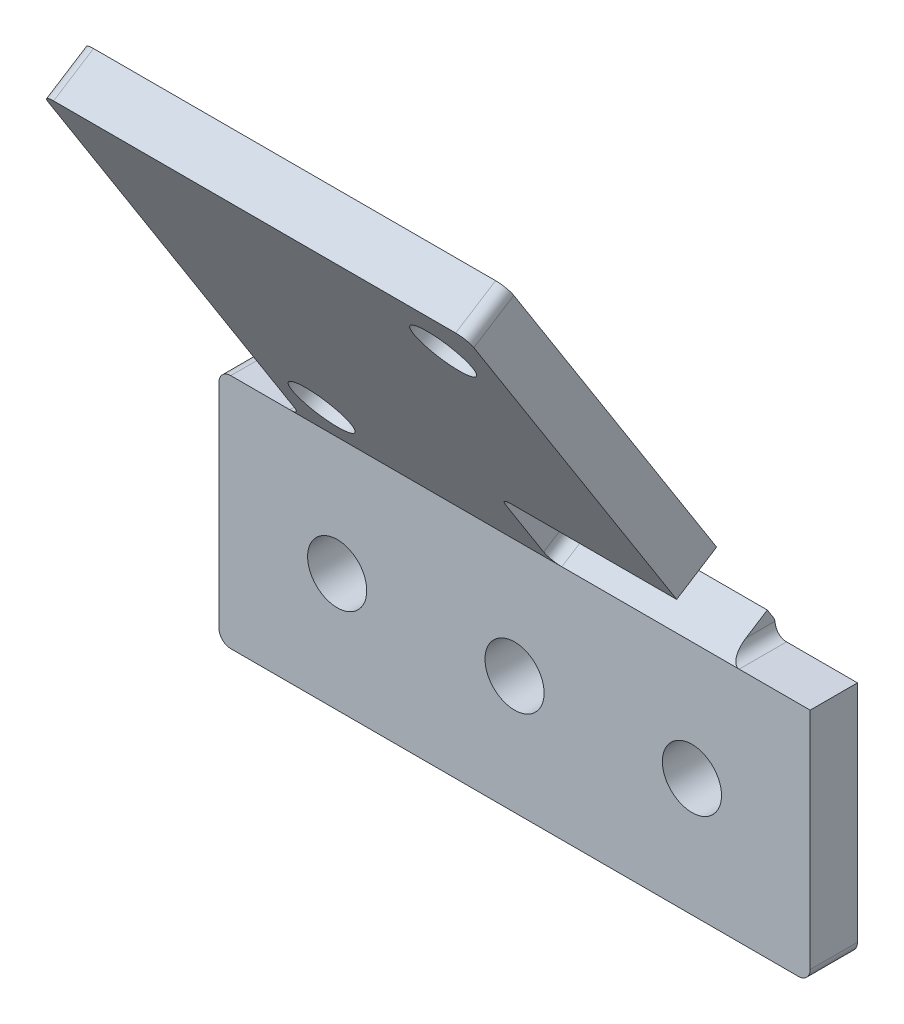
SolidWorks part; units mm, degrees
ref_plane "前视基准面" through (0, 0, 0) normal (0, 0, 1) x (1, 0, 0)
ref_plane "上视基准面" through (0, 0, 0) normal (0, 1, 0) x (1, 0, 0)
ref_plane "右视基准面" through (0, 0, 0) normal (1, 0, 0) x (0, 0, -1)
sketch "草图1" plane through (0, 0, 0) normal (0, 0, 1) x (1, 0, 0)
  line L1 (25, -10) -> (-25, -10)
  line L2 (25, -10) -> (25, 10)
  line L3 (25, 10) -> (-25, 10)
  line L4 (-25, -10) -> (-25, 10)
  line L5 (25, -10) -> (-25, 10) construction
  line L6 (25, 10) -> (-25, -10) construction
  point P0 (0, 0)
  dimension "D1" = 20
  dimension "D2" = 50
extrude "凸台-拉伸1" add sketch "草图1" along normal blind 4
sketch "草图4" plane through (0, 0, 0) normal (1, 0, 0) x (0, 0, -1)
  line L0 (-4, 10) -> (-25.9804, 44.6101)
  line L1 (-25.9804, 44.6101) -> (-22.6038, 46.7546)
  line L2 (-22.6038, 46.7546) -> (0.0489, 11.0858)
  line L3 (0.0489, 11.0858) -> (0, 10)
  line L4 (-4, 10) -> (0, 10)
  dimension "D1" = 145
  dimension "D2" = 41
  dimension "D3" = 4
extrude "凸台-拉伸2" add sketch "草图4" along normal mid plane 36
sketch "草图5" plane through (0, 1.0639, -1.6752) normal (0, -0.5361, 0.8441) x (1, 0, 0)
  line L0 (18, 51.5859) -> (-18, 10.5859) construction
  circle A2 centre (12.7216, 45.5744) radius 1.5
  circle A3 centre (-13.6705, 15.5168) radius 1.5
  dimension "D1" = 8
  dimension "D2" = 3
  dimension "D3" = 3
  dimension "D4" = 40
extrude "切除-拉伸1" cut sketch "草图5" against normal through all contours A2 | A2 | A3 | A3 region at (12.7216, 39.5355, 22.7576) region at (-13.6705, 14.1624, 6.6435)
sketch "草图6" plane through (0, 1.0639, -1.6752) normal (0, -0.5361, 0.8441) x (1, 0, 0)
  line L1 (18, 10.5859) -> (3, 10.5859)
  line L2 (18, 10.5859) -> (18, 18.5859)
  line L3 (18, 18.5859) -> (3, 18.5859)
  line L4 (3, 10.5859) -> (3, 18.5859)
  dimension "D1" = 15
  dimension "D2" = 8
extrude "切除-拉伸2" cut sketch "草图6" against normal through all
fillet "圆角1" radius 1 2 edges at (3, 11.0722, 2.3117) (3, 17.8254, 6.6006)
fillet "圆角2" radius 1 7 edges at (25, -10, 2) (-25, -10, 2) (-18, 45.6824, 24.2921) (18, 45.6824, 24.2921) (-25, 10, 2) (-18, 10, 2) (18, 10, 2)
fillet "圆角3" radius 1 1 edges at (0, 11.0858, -0.0489)
sketch "草图7" plane through (0, 1.0639, -1.6752) normal (0, -0.5361, 0.8441) x (1, 0, 0)
  circle A0 centre (12.7216, 45.5744) radius 2.5
  circle A1 centre (-13.6705, 15.5168) radius 2.5
  dimension "D1" = 5
  dimension "D2" = 5
extrude "切除-拉伸3" cut sketch "草图7" against normal blind 2
sketch "草图8" plane through (0, 0, 4) normal (0, 0, 1) x (1, 0, 0)
  line L0 (0, -10) -> (0, 0) construction
  line L1 (-24, -10) -> (24, -10) construction
  circle A0 centre (0, 0) radius 2.5
  circle A1 centre (15, 0) radius 2.5
  circle A2 centre (-15, 0) radius 2.5
  dimension "D1" = 5
  dimension "D2" = 10
  dimension "D3" = 2
  dimension "D4" = 2
extrude "切除-拉伸4" cut sketch "草图8" against normal through all
